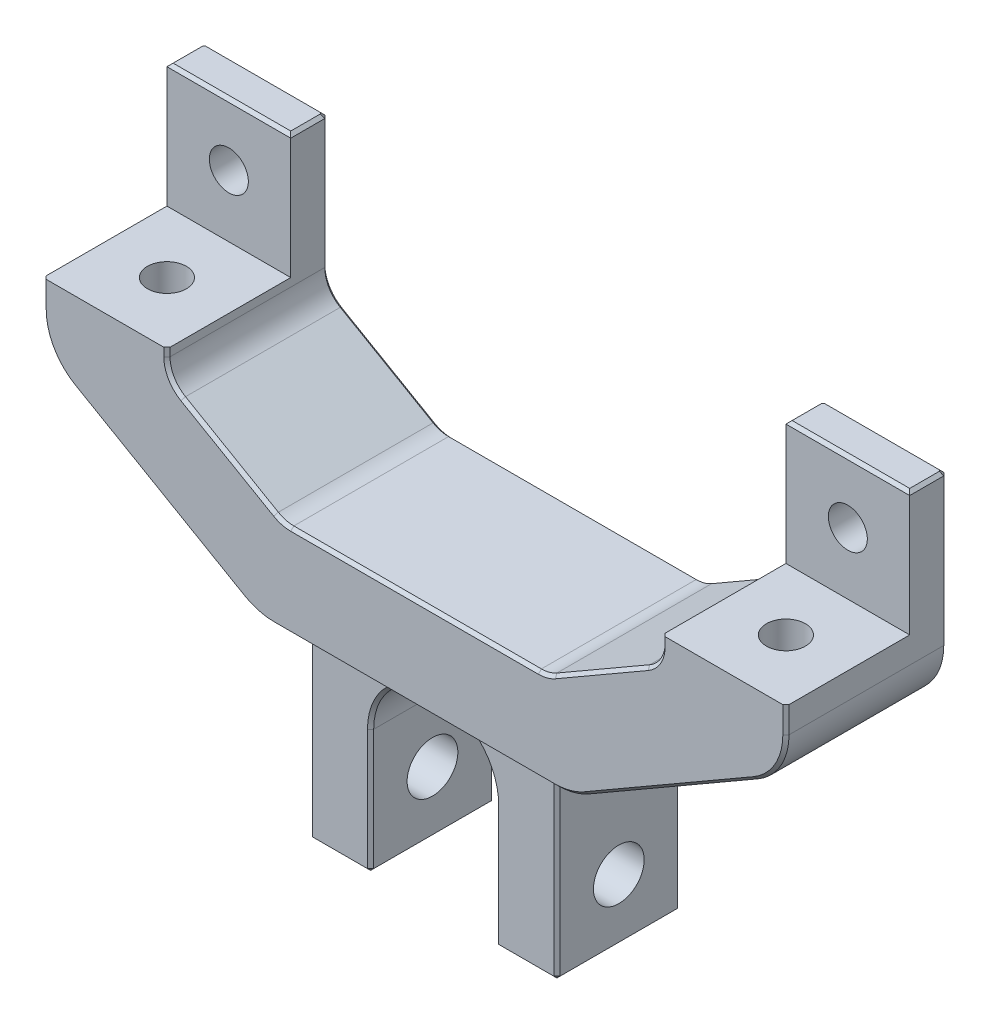
SolidWorks part; units mm, degrees
ref_plane "Front Plane" through (0, 0, 0) normal (0, 0, 1) x (1, 0, 0)
ref_plane "Top Plane" through (0, 0, 0) normal (0, 1, 0) x (1, 0, 0)
ref_plane "Right Plane" through (0, 0, 0) normal (1, 0, 0) x (0, 0, -1)
sketch "Sketch1" plane through (0, 0, 0) normal (0, 0, 1) x (1, 0, 0)
  line L0 (-50, 0) -> (0, 0) construction
  line L1 (-60, -10) -> (-40, -10) construction
  line L2 (-60, -10) -> (-60, 10) construction
  line L3 (-60, 10) -> (-40, 10) construction
  line L4 (-40, -10) -> (-40, 10) construction
  line L5 (-60, -10) -> (-40, 10) construction
  line L6 (-60, 10) -> (-40, -10) construction
  line L7 (-60, 10) -> (-40, 10)
  line L8 (-40, 10) -> (-40, -14.2265)
  line L9 (-40, -14.2265) -> (-21.3397, -25)
  line L10 (-21.3397, -25) -> (0, -25)
  line L11 (0, -25) -> (0, -40)
  line L12 (0, -40) -> (-25.359, -40)
  line L13 (-25.359, -40) -> (-60, -20)
  line L14 (-60, -20) -> (-60, 10)
  point P0 (-50, 0)
  dimension "D1" = 20
  dimension "D2" = 60
  dimension "D3" = 15
  dimension "D4" = 120
  dimension "D5" = 25
  dimension "D6" = 15
  dimension "D7" = 30
extrude "Boss-Extrude1" add sketch "Sketch1" along normal blind 26
sketch "Sketch2" plane through (0, 0, 26) normal (0, 0, 1) x (1, 0, 0)
  line L0 (-40, -14.2265) -> (-40, 10) construction
  line L1 (-60, 10) -> (-40, 10)
  line L2 (-60, 10) -> (-60, -10)
  line L3 (-60, -10) -> (-40, -10)
  line L4 (-40, 10) -> (-40, -10)
  dimension "D1" = 20
extrude "Cut-Extrude1" cut sketch "Sketch2" against normal blind 20
fillet "Fillet1" radius 10 2 edges at (-25.359, -40, 13) (-60, -20, 13)
fillet "Fillet2" radius 5 2 edges at (-21.3397, -25, 13) (-40, -14.2265, 13)
mirror "Mirror1" about plane through (0, -25, 26) normal (-1, 0, 0) of "Fillet2", "Fillet1", "Boss-Extrude1", "Cut-Extrude1"
sketch "Sketch10" plane through (0, 0, 0) normal (0, 0, -1) x (-1, 0, 0)
  line L0 (-50, 10) -> (-50, 0) construction
  line L1 (-40, 10) -> (-60, 10) construction
  line L2 (-50, 0) -> (0, 0) construction
  line L3 (0, 0) -> (50, 0) construction
  line L4 (50, 0) -> (50, 10) construction
  line L5 (40, 10) -> (60, 10) construction
  circle A0 centre (-50, 0) radius 3.15
  circle A1 centre (50, 0) radius 3.15
  dimension "D2" = 6.3
  dimension "D1" = 50
extrude "Cut-Extrude6" cut sketch "Sketch10" against normal through all both
sketch "Sketch11" plane through (0, -10, 0) normal (0, 1, 0) x (1, 0, 0)
  line L0 (0, 0) -> (0, -16) construction
  line L1 (0, -16) -> (50, -16) construction
  line L2 (0, -16) -> (-50, -16) construction
  line L3 (-50, -16) -> (-60, -16) construction
  line L4 (-60, -6) -> (-60, -26) construction
  circle A0 centre (-50, -16) radius 3.15
  circle A1 centre (50, -16) radius 3.15
  dimension "D2" = 6.3
  dimension "D1" = 100
extrude "Cut-Extrude7" cut sketch "Sketch11" against normal blind 10
sketch "Sketch12" plane through (0, -20, 0) normal (0, 1, 0) x (1, 0, 0)
  circle A0 centre (-50, -16) radius 7
  circle A1 centre (50, -16) radius 7
  dimension "D1" = 14
extrude "Cut-Extrude8" cut sketch "Sketch12" against normal through all
sketch "Sketch3" plane through (0, -40, 0) normal (0, -1, 0) x (1, 0, 0)
  line L0 (0, 13) -> (0, 0) construction
  line L1 (-20, 3) -> (20, 3)
  line L2 (-20, 3) -> (-20, 23)
  line L3 (-20, 23) -> (20, 23)
  line L4 (20, 3) -> (20, 23)
  line L5 (-20, 3) -> (20, 23) construction
  line L6 (-20, 23) -> (20, 3) construction
  line L7 (-60, 13) -> (-20, 13) construction
  line L8 (-60, 0) -> (-60, 26) construction
  point P0 (0, 13)
  dimension "D1" = 40
  dimension "D2" = 20
extrude "Boss-Extrude2" add sketch "Sketch3" along normal blind 30
sketch "Sketch4" plane through (0, -70, 0) normal (0, -1, 0) x (1, 0, 0)
  line L0 (20, 23) -> (-20, 23) construction
  line L1 (-10.1, 3) -> (10.1, 3)
  line L2 (-10.1, 3) -> (-10.1, 23)
  line L3 (-10.1, 23) -> (10.1, 23)
  line L4 (10.1, 3) -> (10.1, 23)
  line L5 (-10.1, 3) -> (10.1, 23) construction
  line L6 (-10.1, 23) -> (10.1, 3) construction
  line L7 (-20, 3) -> (20, 3) construction
  line L8 (0, 13) -> (0, 0) construction
  line L9 (-22.6795, 0) -> (22.6795, 0) construction
  point P0 (0, 13)
  dimension "D1" = 20.2
extrude "Cut-Extrude2" cut sketch "Sketch4" against normal blind 30
fillet "Fillet3" radius 10 2 edges at (10.1, -40, 13) (-10.1, -40, 13)
sketch "Sketch5" plane through (0, 0, 0) normal (1, 0, 0) x (0, 0, -1)
  line L0 (-13, -70) -> (-13, -60) construction
  line L1 (-3, -70) -> (-23, -70) construction
  circle A0 centre (-13, -60) radius 4.1
  dimension "D2" = 8.2
  dimension "D1" = 10
extrude "Cut-Extrude3" cut sketch "Sketch5" against normal through all both and the other way through all
sketch "Sketch6" plane through (0, 0, 0) normal (1, 0, 0) x (0, 0, -1)
  line L0 (-26, -25) -> (-46, -59.641)
  line L1 (-46, -59.641) -> (-28.6795, -69.641)
  line L2 (-28.6795, -69.641) -> (-8.6795, -35)
  line L3 (-8.6795, -35) -> (-26, -25)
  line L5 (-6, 10) -> (-6, -10) construction
  point P2 (-24.7176, -27.8016)
  point P5 (-42.1822, -71.898)
  point P6 (-25.3048, -25.949)
  point P7 (-25.3048, -72.3075)
  point P10 (-26, -25)
  dimension "D1" = 30
  dimension "D2" = 20
  dimension "D3" = 40
extrude "Boss-Extrude3" [suppressed] add sketch "Sketch6" along normal mid plane 40
sketch "Sketch7" [suppressed] plane through (0, -64.6493, 37.3253) normal (0, -0.866, 0.5) x (1, 0, 0)
  line L0 (20, 10.0167) -> (-20, 10.0167) construction
  line L1 (-10.1, -10.0167) -> (10.1, -10.0167)
  line L2 (-10.1, -10.0167) -> (-10.1, 10.0167)
  line L3 (-10.1, 10.0167) -> (10.1, 10.0167)
  line L4 (10.1, -10.0167) -> (10.1, 10.0167)
  line L5 (-10.1, -10.0167) -> (10.1, 10.0167) construction
  line L6 (-10.1, 10.0167) -> (10.1, -10.0167) construction
  point P0 (0, 0)
  dimension "D1" = 20.2
extrude "Cut-Extrude4" [suppressed] cut sketch "Sketch7" against normal blind 30
fillet "Fillet4" [suppressed] radius 10
fillet "Fillet5" [suppressed] radius 20
chamfer "Chamfer1" [suppressed] distance 0.5 angle 45
sketch "Sketch8" [suppressed] plane through (0, 0, 0) normal (1, 0, 0) x (0, 0, -1)
  line L0 (-37.3397, -64.641) -> (-32.3397, -55.9808) construction
  line L1 (-28.6795, -69.641) -> (-46, -59.641) construction
  line L2 (-26.683, -26.183) -> (-45.75, -59.208) construction
  circle A0 centre (-32.3397, -55.9808) radius 4.1
  dimension "D1" = 8.2
  dimension "D2" = 10
extrude "Cut-Extrude5" [suppressed] cut sketch "Sketch8" against normal through all both and the other way through all
chamfer "Chamfer2" distance 0.5 angle 45 20 edges at (7.1711, -42.9289, 3) (7.1711, -42.9289, 23) (20, -70, 13) (20, -55, 3) (15.05, -70, 3) (10.1, -60, 3) (10.1, -70, 13) (10.1, -60, 23) (15.05, -70, 23) (20, -55, 23) (-7.1711, -42.9289, 3) (-7.1711, -42.9289, 23) (-20, -70, 13) (-20, -55, 3) (-15.05, -70, 3) (-10.1, -60, 3) (-10.1, -70, 13) (-10.1, -60, 23) (-15.05, -70, 23) (-20, -55, 23)
chamfer "Chamfer3" distance 0.5 angle 45 18 edges at (-60, -2.1132, 0) (-58.6603, -19.2265, 0) (60, -2.1132, 0) (-41.3397, -30.7735, 0) (58.6603, -19.2265, 0) (-25.2677, -39.6593, 0) (41.3397, -30.7735, 0) (0, -40, 0) (25.2677, -39.6593, 0) (60, -12.1132, 26) (58.6603, -19.2265, 26) (-60, -12.1132, 26) (41.3397, -30.7735, 26) (-58.6603, -19.2265, 26) (25.2677, -39.6593, 26) (-41.3397, -30.7735, 26) (0, -40, 26) (-25.2677, -39.6593, 26)
chamfer "Chamfer4" distance 0.5 angle 45 20 edges at (-53.15, 0, 0) (46.85, 0, 0) (-40, -10.6699, 26) (-39.3301, -13.8397, 26) (-30, -20, 26) (-21.2941, -24.8296, 26) (0, -25, 26) (40, -10.6699, 26) (21.2941, -24.8296, 26) (39.3301, -13.8397, 26) (30, -20, 26) (-40, -0.6699, 0) (-39.3301, -13.8397, 0) (-30, -20, 0) (-21.2941, -24.8296, 0) (0, -25, 0) (40, -0.6699, 0) (21.2941, -24.8296, 0) (39.3301, -13.8397, 0) (30, -20, 0)
chamfer "Chamfer5" distance 0.5 angle 45 12 edges at (-50, 10, 6) (-60, 10, 3.25) (-59.75, 10, 0.25) (-50, 10, 0) (-40.25, 10, 0.25) (-40, 10, 3.25) (59.75, 10, 0.25) (60, 10, 3.25) (50, 10, 6) (40, 10, 3.25) (40.25, 10, 0.25) (50, 10, 0)
